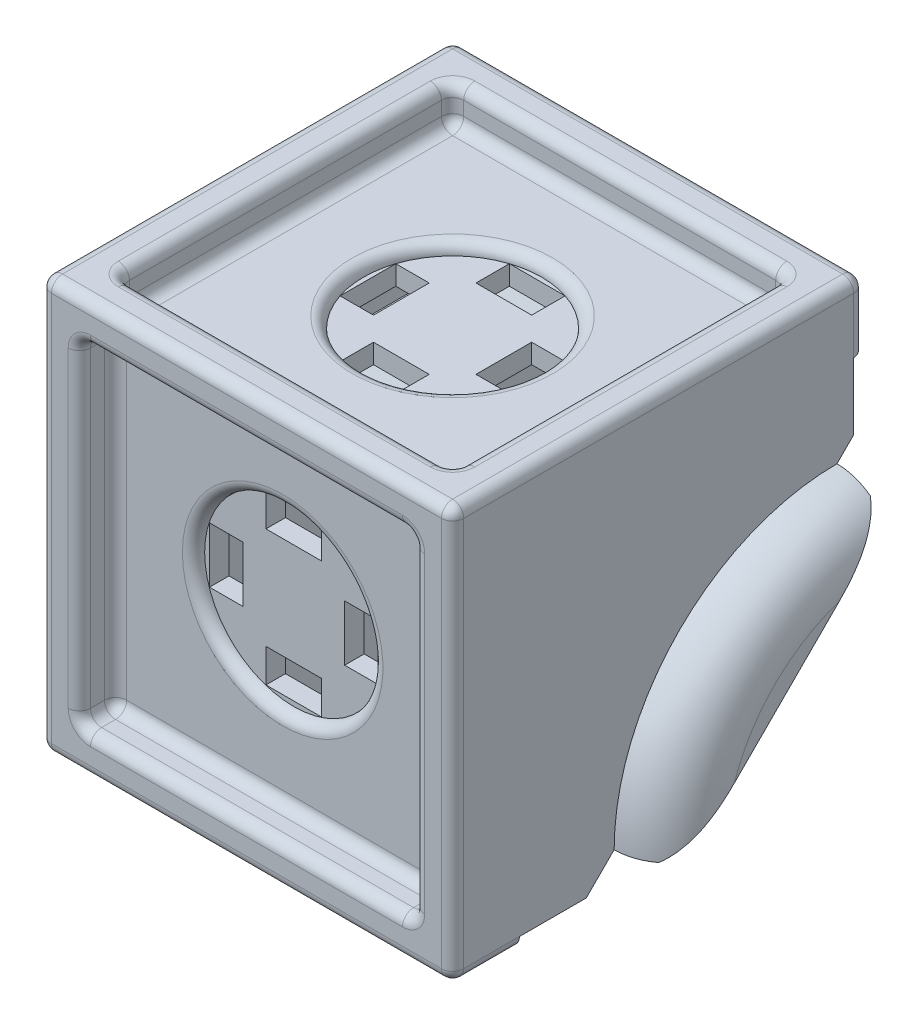
SolidWorks part; units mm, degrees
material "ABS"
ref_plane "Front Plane" through (0, 0, 0) normal (0, 0, 1) x (1, 0, 0)
ref_plane "Top Plane" through (0, 0, 0) normal (0, 1, 0) x (1, 0, 0)
ref_plane "Right Plane" through (0, 0, 0) normal (1, 0, 0) x (0, 0, -1)
sketch "Sketch1" plane through (0, 0, 0) normal (0, 0, 1) x (1, 0, 0)
  line L0 (-9.398, 9.398) -> (-9.398, -9.398)
  line L1 (-9.398, -9.398) -> (9.398, -9.398)
  line L2 (9.398, -9.398) -> (9.398, 9.398)
  line L3 (9.398, 9.398) -> (-9.398, 9.398)
extrude "Boss-Extrude1" add sketch "Sketch1" against normal blind 3.048
ref_plane "Plane1" through (0, 9.398, 0) normal (0, 1, 0) x (1, 0, 0)
sketch "Sketch3" plane through (0, 9.398, 0) normal (0, 1, 0) x (1, 0, 0)
  line L0 (-9.398, 0) -> (-9.398, 18.796)
  line L1 (-9.398, 18.796) -> (9.398, 18.796)
  line L2 (9.398, 18.796) -> (9.398, 0)
  line L3 (9.398, 0) -> (-9.398, 0)
extrude "Boss-Extrude2" add sketch "Sketch3" against normal blind 3.048
sketch "Sketch4" plane through (0, 9.398, 0) normal (0, 1, 0) x (1, 0, 0)
  line L0 (-7.62, 1.778) -> (-7.62, 17.018)
  line L1 (-7.62, 17.018) -> (7.62, 17.018)
  line L2 (7.62, 17.018) -> (7.62, 1.778)
  line L3 (7.62, 1.778) -> (-7.62, 1.778)
extrude "Cut-Extrude1" cut sketch "Sketch4" against normal blind 1.651
sketch "Sketch5" plane through (0, 0, 0) normal (0, 0, 1) x (1, 0, 0)
  line L0 (-7.62, 7.62) -> (7.62, 7.62)
  line L1 (7.62, 7.62) -> (7.62, -7.62)
  line L2 (7.62, -7.62) -> (-7.62, -7.62)
  line L3 (-7.62, -7.62) -> (-7.62, 7.62)
extrude "Cut-Extrude2" cut sketch "Sketch5" against normal blind 1.651
sketch "Sketch6" plane through (0, 7.747, 0) normal (0, 1, 0) x (1, 0, 0)
sketch "Sketch7" plane through (0, 0, 0) normal (0, 0, 1) x (1, 0, 0)
  line L24 (1.27, -3.8427) -> (-1.27, -3.8427)
  line L30 (-1.246, 11.3973) -> (1.3229, 11.3973)
  line L32 (1.27, -3.8427) -> (1.27, -2.3187)
  line L33 (1.27, -2.3187) -> (-1.27, -2.3187)
  line L34 (-1.27, -2.3187) -> (-1.27, -3.8427)
  line L35 (-2.3187, 1.27) -> (-3.8427, 1.27)
  line L36 (-3.8427, -1.27) -> (-3.8427, 1.27)
  line L37 (-3.8427, -1.27) -> (-2.3187, -1.27)
  line L38 (-2.3187, -1.27) -> (-2.3187, 1.27)
  line L39 (1.27, 2.3187) -> (1.27, 3.8427)
  line L40 (-1.27, 3.8427) -> (1.27, 3.8427)
  line L41 (-1.27, 3.8427) -> (-1.27, 2.3187)
  line L42 (-1.27, 2.3187) -> (1.27, 2.3187)
  line L43 (2.3187, -1.27) -> (3.8427, -1.27)
  line L44 (3.8427, 1.27) -> (3.8427, -1.27)
  line L45 (3.8427, 1.27) -> (2.3187, 1.27)
  line L46 (2.3187, 1.27) -> (2.3187, -1.27)
  circle A1 centre (0, 0) radius 4.0471
  point P22 (0, 0)
  point P25 (0, 0)
  dimension "D1" = 1.524
  dimension "D2" = 2.54
  dimension "D3" = 1.27
  dimension "D4" = 4
ref_plane "Plane2" through (9.398, 0, 0) normal (1, 0, 0) x (0, 0, -1)
sketch "Sketch8" plane through (9.398, 0, 0) normal (1, 0, 0) x (0, 0, -1)
  line L0 (3.048, 6.35) -> (3.048, -8.89)
  line L1 (3.048, -9.398) -> (3.048, 6.35) construction
  line L2 (3.048, -8.89) -> (6.096, -8.89)
  line L3 (3.048, 6.35) -> (18.288, 6.35)
  line L4 (3.048, 6.35) -> (18.796, 6.35) construction
  line L5 (18.288, 6.35) -> (18.288, 3.302)
  line L6 (6.096, -8.89) -> (7.366, -7.62)
  line L7 (7.366, -7.62) -> (7.874, -7.62)
  line L8 (7.874, -7.62) -> (17.526, 2.032)
  line L9 (17.526, 2.54) -> (17.526, 2.032)
  line L10 (17.526, 2.54) -> (18.288, 3.302)
  dimension "D1" = 15.24
  dimension "D2" = 15.24
  dimension "D3" = 3.048
  dimension "D4" = 3.048
  dimension "D5" = 1.27
  dimension "D6" = 1.27
extrude "Boss-Extrude3" add sketch "Sketch8" against normal blind 1.651
fillet "Fillet1" radius 0.508 4 edges at (-7.62, 8.5725, -1.778) (7.62, 8.5725, -1.778) (7.62, 8.5725, -17.018) (-7.62, 8.5725, -17.018)
fillet "Fillet2" radius 0.508 4 edges at (-7.62, 7.62, -0.8255) (7.62, -7.62, -0.8255) (-7.62, -7.62, -0.8255) (7.62, 7.62, -0.8255)
mirror "Mirror1" about plane through (0, 0, 0) normal (1, 0, 0) of "Boss-Extrude3"
extrude "Cut-Extrude5" cut sketch "Sketch7" against normal blind 5.08 contours L41 L42 L39 L40 | L45 L46 L43 L44 | L33 L34 L24 L32 | L37 L38 L35 L36 region at (0, -3.0807, 0) region at (3.0807, 0, 0) region at (-3.0807, 0, 0) region at (0, 3.0807, 0)
sketch "Sketch11" plane through (0, 9.398, 0) normal (0, 1, 0) x (1, 0, 0)
  line L0 (0, 18.796) -> (0, 0) construction
  line L1 (9.398, 18.796) -> (-9.398, 18.796) construction
  line L10 (-4.9408, 9.398) -> (5.0621, 9.398) construction
  line L11 (-1.27, 13.2585) -> (1.27, 13.2585)
  line L12 (1.27, 13.2585) -> (1.27, 11.7345)
  line L13 (1.27, 11.7345) -> (-1.27, 11.7345)
  line L14 (-1.27, 11.7345) -> (-1.27, 13.2585)
  line L15 (3.8605, 10.668) -> (3.8605, 8.128)
  line L16 (3.8605, 8.128) -> (2.3365, 8.128)
  line L17 (2.3365, 8.128) -> (2.3365, 10.668)
  line L18 (2.3365, 10.668) -> (3.8605, 10.668)
  line L19 (1.27, 5.5375) -> (-1.27, 5.5375)
  line L20 (-1.27, 5.5375) -> (-1.27, 7.0615)
  line L21 (-1.27, 7.0615) -> (1.27, 7.0615)
  line L22 (1.27, 7.0615) -> (1.27, 5.5375)
  line L23 (-3.8605, 8.128) -> (-2.3365, 8.128)
  line L24 (-2.3365, 8.128) -> (-2.3365, 10.668)
  line L25 (-2.3365, 10.668) -> (-3.8605, 10.668)
  line L26 (-3.8605, 10.668) -> (-3.8605, 8.128)
  circle A0 centre (0, 9.398) radius 4.064
  dimension "D1" = 1.524
  dimension "D4" = 8.128
  dimension "D2" = 2.54
  dimension "D3" = 1.524
  dimension "D5" = 2.54
  dimension "D6" = 1.524
  dimension "D7" = 1.524
extrude "Cut-Extrude6" cut sketch "Sketch11" against normal blind 5.08 contours L14 L13 L12 L11 | L18 L17 L16 L15 | L22 L21 L20 L19 | L25 L26 L23 L24 region at (0, 9.398, -12.4965) region at (-3.0985, 9.398, -9.398) region at (3.0985, 9.398, -9.398) region at (0, 9.398, -6.2995)
sketch "Sketch12" plane through (0, 7.747, 0) normal (0, 1, 0) x (1, 0, 0)
  line L0 (-7.62, 9.398) -> (7.62, 9.398) construction
  line L1 (-7.62, 16.51) -> (-7.62, 2.286) construction
  line L2 (7.62, 2.286) -> (7.62, 16.51) construction
  circle A0 centre (0, 9.398) radius 4.064
extrude "Cut-Extrude7" cut sketch "Sketch12" against normal blind 0.508
fillet "Fillet3" radius 0.508 1 edges at (0, 7.747, -5.334)
fillet "Fillet4" radius 0.508 32 edges at (-7.4712, 7.4712, -1.651) (0, 7.62, -1.651) (7.4712, 7.4712, -1.651) (7.62, 0, -1.651) (7.4712, -7.4712, -1.651) (0, -7.62, -1.651) (-7.4712, -7.4712, -1.651) (7.4712, 7.4712, 0) (7.62, 0, 0) (7.4712, -7.4712, 0) (0, -7.62, 0) (-7.4712, -7.4712, 0) (-7.62, 0, 0) (-7.4712, 7.4712, 0) (7.4712, 7.747, -16.8692) (7.62, 7.747, -9.398) (7.4712, 7.747, -1.9268) (0, 7.747, -1.778) (-7.4712, 7.747, -1.9268) (-7.62, 7.747, -9.398) (-7.4712, 7.747, -16.8692) (7.4712, 9.398, -16.8692) (7.62, 9.398, -9.398) (7.4712, 9.398, -1.9268) (0, 9.398, -1.778) (-7.4712, 9.398, -1.9268) (-7.62, 9.398, -9.398) (-7.4712, 9.398, -16.8692) (-7.62, 0, -1.651) (0, 7.62, 0) (0, 7.747, -17.018) (0, 9.398, -17.018)
sketch "Sketch13" plane through (0, 0, 0) normal (0, 0, 1) x (1, 0, 0)
  circle A0 centre (0, 0) radius 4.064
extrude "Cut-Extrude8" cut sketch "Sketch13" against normal blind 2.159
fillet "Fillet5" radius 0.508 1 edges at (-4.064, 0, -1.651)
fillet "Fillet6" radius 0.508 11 edges at (-9.398, -9.398, -1.524) (-9.398, 7.874, -18.796) (0, 9.398, -18.796) (-9.398, 9.398, -9.398) (-9.398, 0, 0) (9.398, 7.874, -18.796) (9.398, -9.398, -1.524) (0, -9.398, 0) (9.398, 0, 0) (9.398, 9.398, -9.398) (0, 9.398, 0)
sketch "Sketch14" plane through (0, 0, -3.048) normal (0, 0, -1) x (-1, 0, 0)
  line L0 (0, 5.7276) -> (0, -6.1) construction
  line L2 (-7.747, 0.9625) -> (-2.1786, 1.8134)
  line L3 (-7.747, 6.35) -> (-7.747, -8.89) construction
  line L4 (7.747, 0.9625) -> (2.1786, 1.8134)
  line L5 (-2.1786, 1.8134) -> (-2.1786, -6.1)
  line L6 (2.1786, 1.8134) -> (2.1786, -6.1)
  line L7 (-2.1786, -6.1) -> (-7.747, -6.1)
  line L8 (2.1786, -6.1) -> (7.747, -6.1)
  line L9 (-7.747, -6.1) -> (-7.747, -7.1211)
  line L10 (7.747, -6.1) -> (7.747, -7.1211)
  line L11 (-7.747, -7.1211) -> (-1.583, -7.1211)
  line L12 (7.747, -7.1211) -> (1.583, -7.1211)
  line L13 (-1.583, -6.1) -> (-1.583, 2.8345)
  line L14 (1.583, -6.1) -> (1.583, 2.8345)
  line L15 (-1.583, 2.8345) -> (-7.747, 1.8926)
  line L16 (1.583, 2.8345) -> (7.747, 1.8926)
  line L17 (-7.747, 1.8926) -> (-7.747, 0.9625)
  line L18 (7.747, 1.8926) -> (7.747, 0.9625)
  line L19 (-1.583, -6.1) -> (1.583, -6.1)
  line L20 (-1.583, -7.1211) -> (1.583, -7.1211)
extrude "Boss-Extrude4" add sketch "Sketch14" along normal blind 15.24
sketch "Sketch15" plane through (2.1786, 0, 0) normal (1, 0, 0) x (0, 0, -1)
  line L0 (9.0298, -13.2627) -> (9.0298, 1.135)
  line L1 (9.0298, 1.135) -> (23.0041, 1.135)
  line L2 (23.0041, 1.135) -> (23.0041, 0.2528)
  line L3 (9.9826, -13.2627) -> (9.0298, -13.2627)
  arc A0 (23.0041, 0.2528) -> (9.9826, -13.2627) centre (23.0041, -12.7777) ccw
extrude "Boss-Extrude5" add sketch "Sketch15" against normal blind 4.3561
sketch "Sketch16" plane through (2.1786, 0, 0) normal (1, 0, 0) x (0, 0, -1)
  line L0 (23.0041, 0.2528) -> (23.0041, -12.7777)
  line L1 (23.0041, -12.7777) -> (9.9735, -12.7777)
  arc A0 (11.2654, -7.1211) -> (9.9826, -13.2627) centre (23.0041, -12.7777) ccw construction
  arc A1 (9.9735, -12.7777) -> (23.0041, 0.2528) centre (23.0041, -12.7777) cw
extrude "Cut-Extrude11" cut sketch "Sketch16" against normal mid plane 25.4
sketch "Sketch17" plane through (9.398, 0, 0) normal (1, 0, 0) x (0, 0, -1)
  line L0 (7.874, -7.62) -> (7.366, -7.62)
  line L1 (17.526, 2.54) -> (17.526, 2.032)
  line L2 (17.526, 2.032) -> (17.526, 2.54) construction
  line L3 (17.526, 2.032) -> (7.874, -7.62)
  arc A0 (7.366, -7.62) -> (17.526, 2.54) centre (17.526, -7.62) cw
extrude "Boss-Extrude6" add sketch "Sketch17" along normal blind 2.54
fillet "Fillet9" radius 2.54 1 edges at (11.938, -0.4358, -10.3418)
mirror "Mirror2" about plane through (0, 0, 0) normal (1, 0, 0) of "Boss-Extrude3"
sketch "Sketch19" plane through (-9.398, 0, 0) normal (-1, 0, 0) x (0, 0, 1)
  line L0 (-17.526, 2.032) -> (-17.526, 2.54)
  line L1 (-7.366, -7.62) -> (-7.874, -7.62)
  line L2 (-7.874, -7.62) -> (-17.526, 2.032)
  arc A0 (-17.526, 2.54) -> (-7.366, -7.62) centre (-17.526, -7.62) cw
extrude "Boss-Extrude7" add sketch "Sketch19" along normal blind 2.54
fillet "Fillet11" radius 2.54 1 edges at (-11.938, -0.4358, -10.3418)
